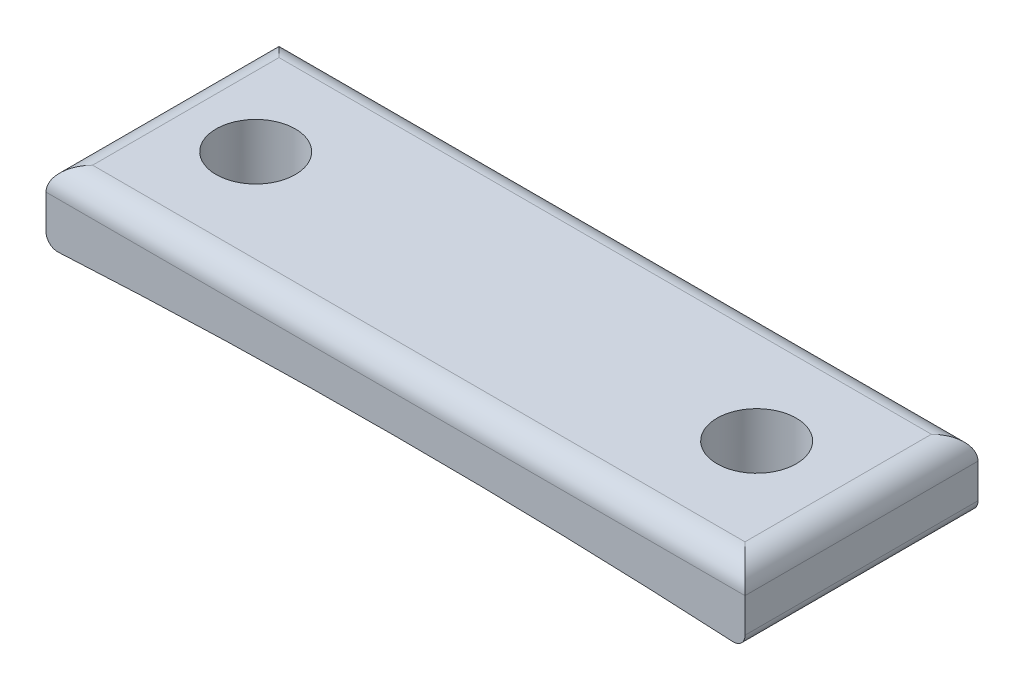
SolidWorks part; units mm, degrees
ref_plane "Front Plane" through (0, 0, 0) normal (0, 0, 1) x (1, 0, 0)
ref_plane "Top Plane" through (0, 0, 0) normal (0, 1, 0) x (1, 0, 0)
ref_plane "Right Plane" through (0, 0, 0) normal (1, 0, 0) x (0, 0, -1)
sketch "Sketch1" plane through (0, 0, 0) normal (0, 1, 0) x (1, 0, 0)
  line L0 (-6.2308, 3) -> (-6.2308, -7)
  line L1 (-6.2308, 3) -> (23.7692, 3)
  line L2 (-6.2308, -7) -> (23.7692, -7)
  line L3 (23.7692, 3) -> (23.7692, -7)
  dimension "D1" = 30
  dimension "D2" = 10
extrude "Boss-Extrude1" add sketch "Sketch1" along normal blind 3
hole_wizard "M3 Clearance Hole1" positions "Sketch4" profile "Sketch6" hole size "M3" standard "ISO" end condition through all
sketch "Sketch4" plane through (0, 3, 0) normal (0, 1, 0) x (1, 0, 0)
  line L0 (-6.2308, 3) -> (-6.2308, -7) construction
  line L2 (23.7692, 3) -> (-6.2308, 3) construction
  line L4 (23.7692, -7) -> (23.7692, 3) construction
  point P0 (-2.2308, -2)
  point P2 (19.2692, -2)
  dimension "D1" = 4
  dimension "D2" = 4.5
  dimension "D3" = 5
  dimension "D4" = 5
sketch "Sketch6" plane through (-2.2308, 3, 2) normal (1, 0, 0) x (0, 0, 1)
  line L0 (0, 0) -> (0, 3)
  line L1 (0, 3) -> (1.7, 3)
  line L2 (1.7, 3) -> (1.7, 0)
  line L5 (1.7, 0) -> (0, 0)
  line L11 (0, -6.35) -> (0, 107.95) construction
  dimension "Thru Hole Dia." = 3.4
  dimension "Thru Hole Depth" = 3
fillet "Fillet3" radius 1 4 edges at (-6.2308, 3, 2) (8.7692, 3, 7) (23.7692, 3, 2) (8.7692, 3, -3)
sketch "Sketch8" plane through (0, 0, 7) normal (0, 0, 1) x (1, 0, 0)
  arc A0 (-6.2308, 0) -> (23.7692, 0) centre (8.7692, -263.6509) cw
extrude "Cut-Extrude4" cut sketch "Sketch8" against normal through all and the other way through all flip side to cut contours A0
fillet "Fillet4" radius 0.5 2 edges at (23.7692, 0, 2) (-6.2308, 0, 2)
